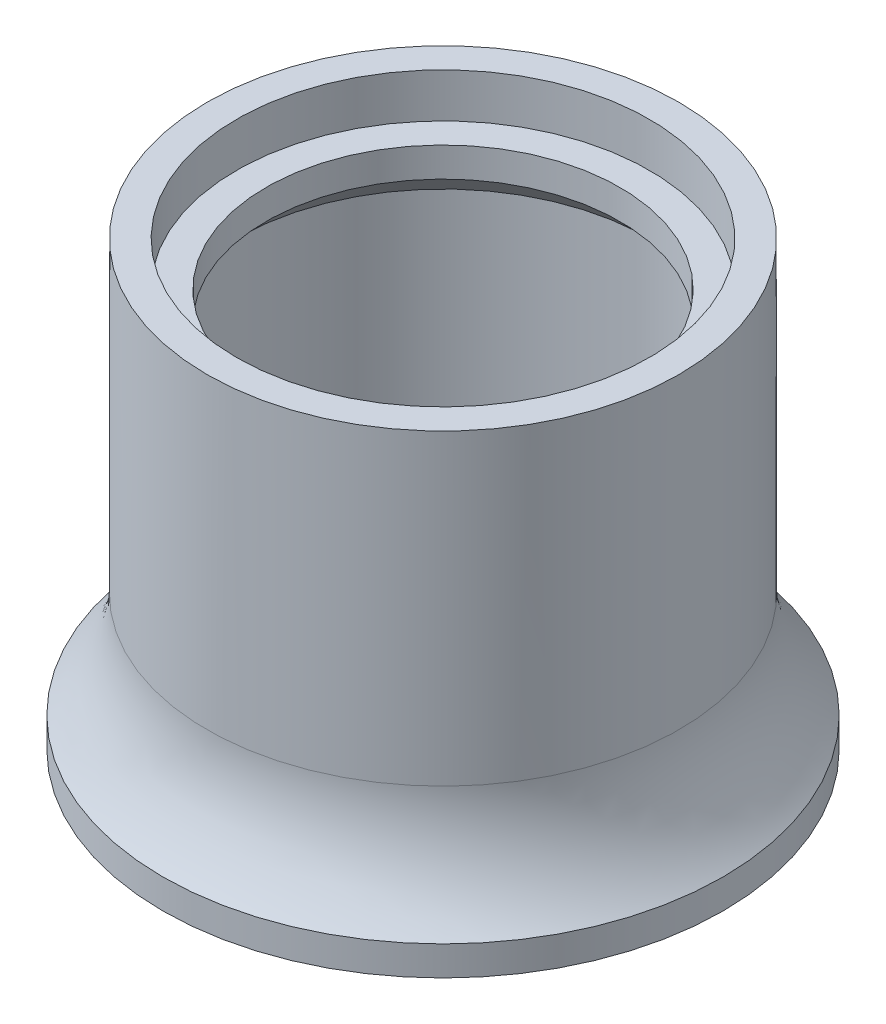
SolidWorks part; units mm, degrees
ref_plane "Front Plane" through (0, 0, 0) normal (0, 0, 1) x (1, 0, 0)
ref_plane "Top Plane" through (0, 0, 0) normal (0, 1, 0) x (1, 0, 0)
ref_plane "Right Plane" through (0, 0, 0) normal (1, 0, 0) x (0, 0, -1)
sketch "Sketch1" plane through (0, 0, 0) normal (0, 1, 0) x (1, 0, 0)
  circle A0 centre (0, 0) radius 16
  circle A1 centre (0, 0) radius 14
  dimension "D1" = 32
  dimension "D2" = 2
extrude "Boss-Extrude1" add sketch "Sketch1" along normal blind 30
ref_plane "Plane1" through (0, 2, 0) normal (0, -1, 0) x (-1, 0, 0)
ref_plane "Plane2" through (0, 27, 0) normal (0, 1, 0) x (1, 0, 0)
sketch "Sketch3" plane through (0, 27, 0) normal (0, 1, 0) x (1, 0, 0)
  circle A0 centre (0, 0) radius 14 construction
  circle A1 centre (0, 0) radius 14
  circle A2 centre (0, 0) radius 12
  dimension "D1" = 2
extrude "Boss-Extrude3" add sketch "Sketch3" against normal blind 2
chamfer "Chamfer1" distance 2 angle 45 1 edges at (0, 25, 14)
sketch "Sketch4" plane through (0, 2, 0) normal (0, -1, 0) x (-1, 0, 0)
  circle A0 centre (0, 0) radius 16 construction
  circle A1 centre (0, 0) radius 16
  circle A2 centre (0, 0) radius 19
  dimension "D1" = 3
extrude "Boss-Extrude4" add sketch "Sketch4" along normal up to surface (2 mm away) up to face at (0, 0, 16)
fillet "Fillet2" radius 10 1 edges at (0, 2, -16)
